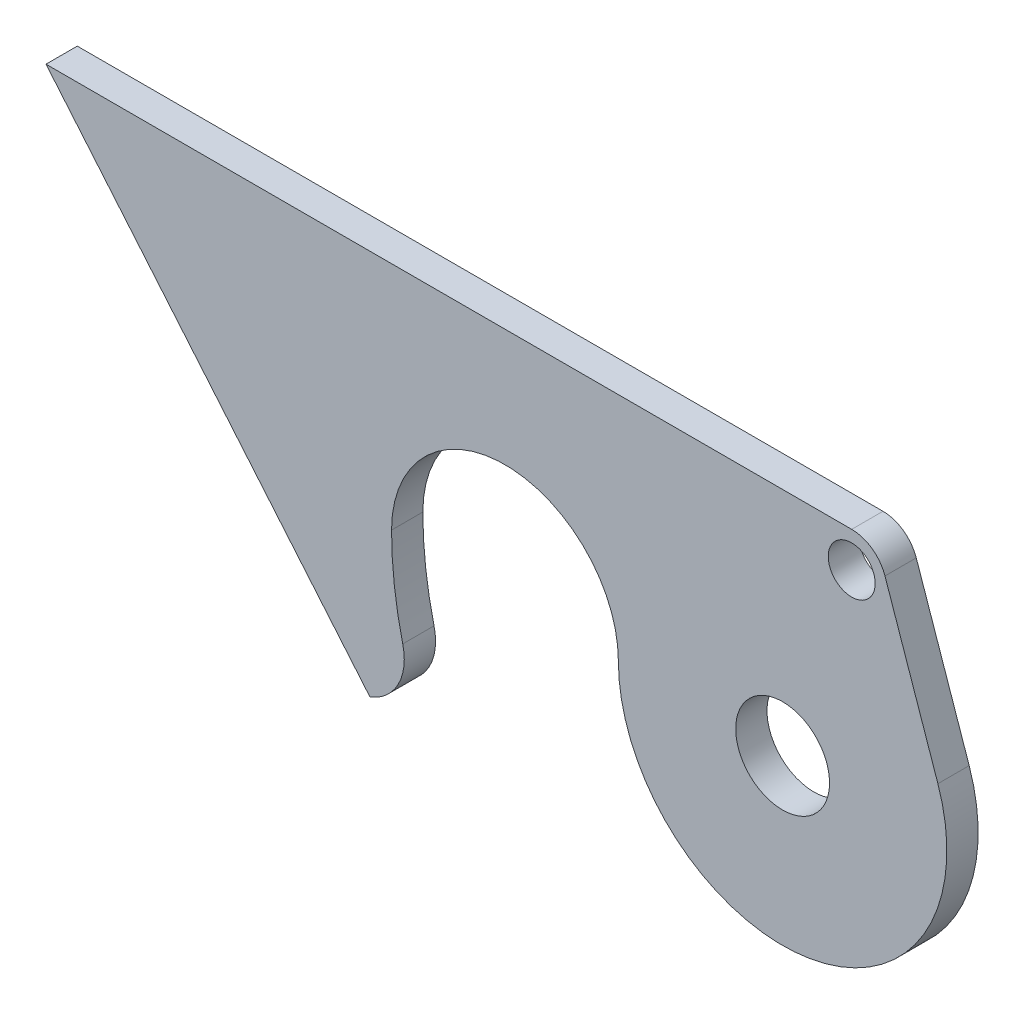
SolidWorks part; units mm, degrees
material "AISI 1020"
ref_plane "Спереди" through (0, 0, 0) normal (0, 0, 1) x (1, 0, 0)
ref_plane "Сверху" through (0, 0, 0) normal (0, 1, 0) x (1, 0, 0)
ref_plane "Справа" through (0, 0, 0) normal (1, 0, 0) x (0, 0, -1)
sketch "Эскиз1" plane through (0, 0, 0) normal (0, 0, 1) x (1, 0, 0)
  line L1 (-94.1802, 29.5) -> (0, 29.5) construction
  line L2 (-52.7689, -19.852) -> (-94.1802, 29.5) construction
  line L4 (-94.1802, 29.5) -> (0, 29.5)
  line L5 (-52.7689, -19.852) -> (-94.1802, 29.5)
  line L9 (0, 29.5) -> (8.8327, 29.5)
  line L10 (13.0869, 26.467) -> (19.8528, 6.8458)
  arc A0 (-21, 0) -> (14.7487, 14.9492) centre (0, 0) ccw construction
  arc A1 (-52.7689, -19.852) -> (-48.5665, -11.8866) centre (-55.1586, -13.5) ccw construction
  arc A2 (-50, 0) -> (-48.5665, -11.8866) centre (0, 0) ccw construction
  arc A3 (-21, 0) -> (19.8528, 6.8458) centre (0, 0) ccw
  arc A4 (-52.7689, -19.852) -> (-48.5665, -11.8866) centre (-55.1586, -13.5) ccw
  arc A5 (-50, 0) -> (-48.5665, -11.8866) centre (0, 0) ccw
  circle A6 centre (-35.5, 0) radius 14.5 construction
  arc A7 (-21, 0) -> (-50, 0) centre (-35.5, 0) ccw
  circle A8 centre (0, 0) radius 6 construction
  circle A9 centre (0, 0) radius 6
  arc A10 (13.0869, 26.467) -> (8.8327, 29.5) centre (8.8327, 25) ccw
  circle A13 centre (8.8327, 25) radius 3 construction
  circle A15 centre (8.8327, 25) radius 3
base flange "Базовая кромка1" sketch "Эскиз1" thickness 4 reverse thickness direction no parameters "D1"=0.74
sketch "Сгиб-Линии1" plane through (0, 0, 0) normal (0, 1, 0) x (1, 0, 0)
sketch "Граничная рамка1" plane through (0, 0, 0) normal (0, 1, 0) x (1, 0, 0)
sheet metal parameters "Листовой металл3" thickness 4 parameters "D1"=0.74
flat pattern "Развертка3" [suppressed]
sketch "Сгиб-Линии2" plane through (0, 0, 0) normal (0, 1, 0) x (1, 0, 0)
sketch "Граничная рамка2" [suppressed] plane through (0, 0, 0) normal (0, 1, 0) x (1, 0, 0)
